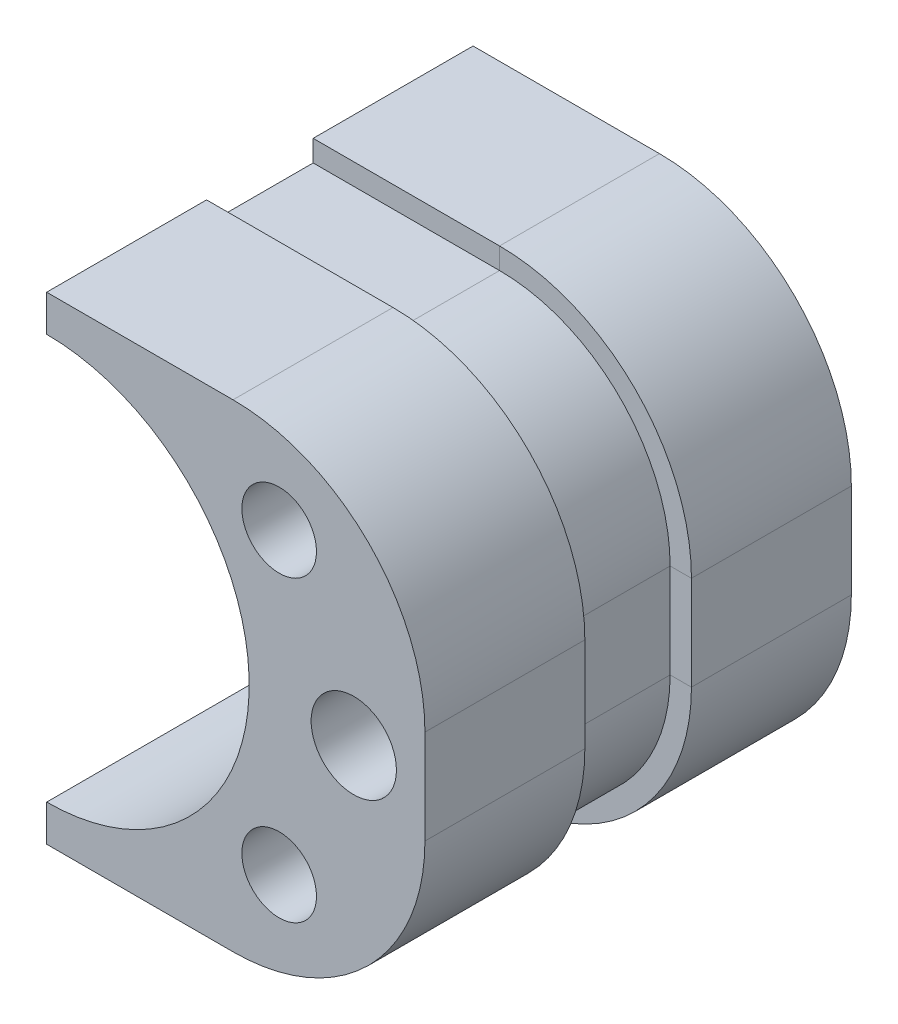
SolidWorks part; units mm, degrees
material "ABS"
ref_plane "Plano frontal" through (0, 0, 0) normal (0, 0, 1) x (1, 0, 0)
ref_plane "Plano superior" through (0, 0, 0) normal (0, 1, 0) x (1, 0, 0)
ref_plane "Plano direito" through (0, 0, 0) normal (1, 0, 0) x (0, 0, -1)
sketch "Esboço1" plane through (0, 0, 0) normal (0, 0, 1) x (1, 0, 0)
  line L0 (0.1126, 0) -> (53.4799, 0) construction
  line L2 (0.1126, -22.4239) -> (0.1126, -19)
  line L6 (0.1126, 19) -> (0.1126, 22.4239)
  line L7 (0.1126, 22.4239) -> (17.5982, 22.4239)
  line L8 (35.5982, 4.4239) -> (35.5982, -4.4239)
  line L9 (0.1126, -22.4239) -> (17.5982, -22.4239)
  arc A0 (0.1126, -19) -> (0.1126, 19) centre (0.1126, 0) ccw
  circle A1 centre (21.9232, -14) radius 1.3931
  circle A3 centre (21.9232, 14) radius 1.3931
  circle A4 centre (28.9232, 0) radius 4
  arc A5 (17.5982, 22.4239) -> (35.5982, 4.4239) centre (17.5982, 4.4239) cw
  arc A6 (35.5982, -4.4239) -> (17.5982, -22.4239) centre (17.5982, -4.4239) cw
  point P0 (28.9232, 0)
  point P1 (0.1126, 0)
  dimension "D3" = 19
  dimension "D6" = 17.4856
  dimension "D4" = 28.8106
  dimension "D5" = 18
  dimension "D1" = 7
  dimension "D2" = 14
extrude "Ressalto-extrusão1" add sketch "Esboço1" along normal blind 40 contours A0 L0 A4 L8 A5 L7 L6 A3 | L0 A0 L2 L9 A6 L8 A4 A1
sketch "Esboço8" plane through (0.1126, 0, 0) normal (-1, 0, 0) x (0, 0, 1)
  line L0 (40, 22.4239) -> (0, 22.4239) construction
  line L5 (15, 22.4239) -> (25, 22.4239)
  line L6 (15, 22.4239) -> (15, 20.4239)
  line L7 (15, 20.4239) -> (25, 20.4239)
  line L8 (25, 22.4239) -> (25, 20.4239)
  point P0 (20, 22.4239)
  point P1 (20, 22.4239)
  dimension "D3" = 2
  dimension "D4" = 10
sketch "Esboço9" plane through (0, 0, 40) normal (0, 0, 1) x (1, 0, 0)
  line L10 (0.1126, -19) -> (0.1126, -22.4239)
  line L11 (0.1126, -22.4239) -> (17.5982, -22.4239)
  line L12 (35.5982, -4.4239) -> (35.5982, 4.4239)
  line L13 (17.5982, 22.4239) -> (0.1126, 22.4239)
  line L14 (0.1126, 22.4239) -> (0.1126, 19)
  line L16 (0.1126, -22.4239) -> (17.5982, -22.4239)
  line L17 (35.5982, -4.4239) -> (35.5982, 4.4239)
  line L18 (17.5982, 22.4239) -> (0.1126, 22.4239)
  arc A6 (0.1126, -19) -> (0.1126, 19) centre (0.1126, 0) ccw
  arc A7 (17.5982, -22.4239) -> (35.5982, -4.4239) centre (17.5982, -4.4239) ccw
  arc A8 (35.5982, 4.4239) -> (17.5982, 22.4239) centre (17.5982, 4.4239) ccw
  arc A10 (17.5982, -22.4239) -> (35.5982, -4.4239) centre (17.5982, -4.4239) ccw
  arc A11 (35.5982, 4.4239) -> (17.5982, 22.4239) centre (17.5982, 4.4239) ccw
  dimension "D1" = 0
sweep "Varredura de corte1" cut profiles "Esboço8" path "Esboço9"
sketch "Esboço10" plane through (0, 0, 40) normal (0, 0, 1) x (1, 0, 0)
  circle A1 centre (21.9232, 14) radius 3.5
  circle A2 centre (21.9232, -14) radius 3.5
  dimension "D1" = 7
extrude "Corte-extrusão1" cut sketch "Esboço10" against normal blind 10
